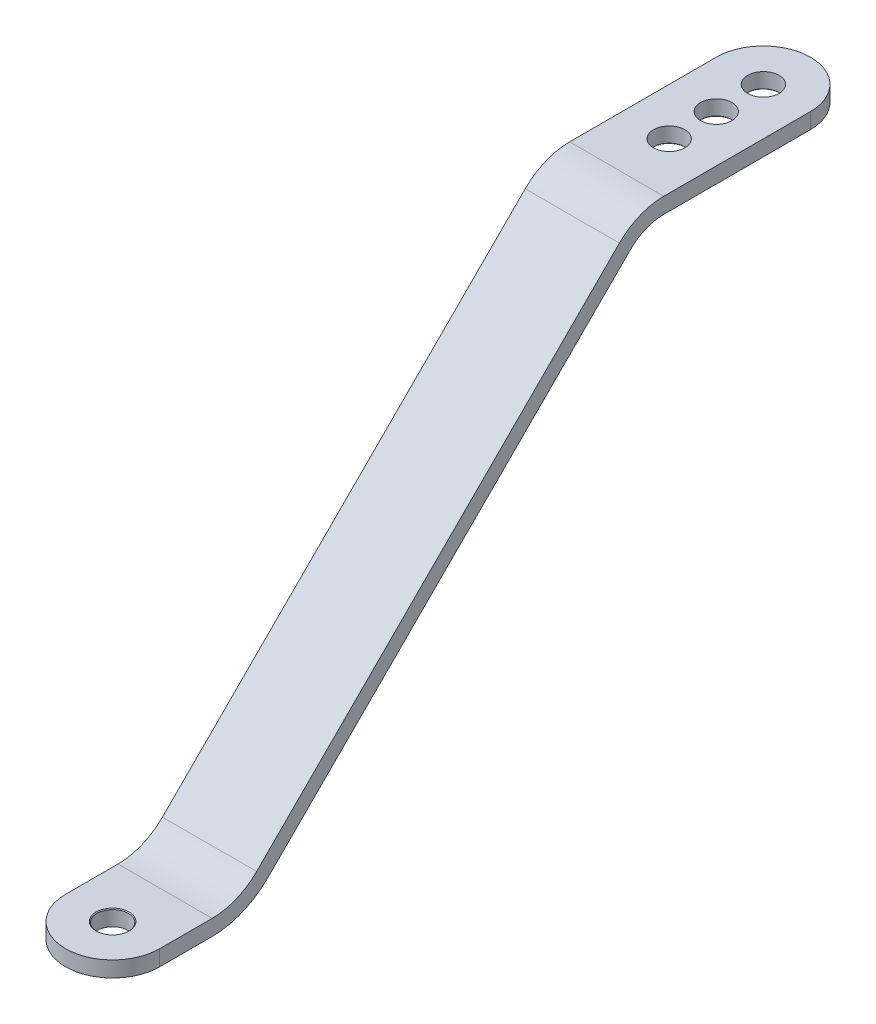
SolidWorks part; units mm, degrees
ref_plane "Front Plane" through (0, 0, 0) normal (0, 0, 1) x (1, 0, 0)
ref_plane "Top Plane" through (0, 0, 0) normal (0, 1, 0) x (1, 0, 0)
ref_plane "Right Plane" through (0, 0, 0) normal (1, 0, 0) x (0, 0, -1)
sketch "Sketch2" plane through (0, 0, 0) normal (1, 0, 0) x (0, 0, -1)
  line L0 (-263.2446, 0) -> (-182.6867, 0)
  line L1 (-146.7656, 14.879) -> (146.7656, 308.4102)
  line L2 (182.6867, 323.2892) -> (339.4446, 323.2892)
  line L3 (0, 0) -> (339.4446, 0) construction
  line L4 (-263.2446, -12.7) -> (-182.6867, -12.7)
  line L5 (-137.7854, 5.8987) -> (155.7459, 299.43)
  line L6 (182.6867, 310.5892) -> (339.4446, 310.5892)
  line L7 (-263.2446, 0) -> (-263.2446, -12.7)
  line L8 (339.4446, 323.2892) -> (339.4446, 310.5892)
  arc A0 (146.7656, 308.4102) -> (182.6867, 323.2892) centre (182.6867, 272.4892) cw
  arc A1 (-182.6867, 0) -> (-146.7656, 14.879) centre (-182.6867, 50.8) ccw
  arc A2 (-182.6867, -12.7) -> (-137.7854, 5.8987) centre (-182.6867, 50.8) ccw
  arc A3 (155.7459, 299.43) -> (182.6867, 310.5892) centre (182.6867, 272.4892) cw
  point P9 (0, 161.6446)
  point P14 (161.6446, 323.2892)
  point P17 (-161.6446, 0)
  dimension "D5" = 50.8
  dimension "D1" = 101.6
  dimension "D2" = 457.2
  dimension "D3" = 177.8
  dimension "D4" = 45
  dimension "D6" = 12.7
extrude "Boss-Extrude1" add sketch "Sketch2" along normal blind 76.2
fillet "Fillet1" 2 edges at (76.2, -6.35, 263.2446) (0, -6.35, 263.2446) type full round first side face at (76.2, 155.7657, -14.2584) second side face at (0, 155.7657, -14.2584) middle face at (38.1, -6.35, 263.2446)
fillet "Fillet2" 2 edges at (0, 316.9392, -339.4446) (76.2, 316.9392, -339.4446) type full round first side face at (0, 155.7657, -20.6084) second side face at (76.2, 155.7657, -20.6084) middle face at (38.1, 316.9392, -339.4446)
hole_wizard "1 (1) Diameter Hole1" positions "Sketch3" profile "Sketch4" hole size "1" standard "ANSI Inch" end condition through all
sketch "Sketch3" plane through (0, 0, 0) normal (0, 1, 0) x (1, 0, 0)
  point P0 (38.1, -225.1446)
sketch "Sketch4" plane through (38.1, 0, 225.1446) normal (1, 0, 0) x (0, 0, 1)
  line L0 (0, 0) -> (0, 12.7)
  line L1 (0, 12.7) -> (12.7, 12.7)
  line L2 (12.7, 12.7) -> (12.7, 0.635)
  line L3 (12.7, 0.635) -> (13.335, 0)
  line L5 (13.335, 0) -> (0, 0)
  line L6 (-12.7, 0.635) -> (-13.335, 0) construction
  line L11 (0, -6.35) -> (0, 107.95) construction
  dimension "Thru Hole Dia." = 25.4
  dimension "Thru Hole Depth" = 12.7
  dimension "Near C'Sink Dia." = 26.67
  dimension "Near C'Sink Angle" = 90
hole_wizard "1 (1) Diameter Hole2" positions "3DSketch1" profile "Sketch7" hole size "1" standard "ANSI Inch" end condition through all
sketch3d "3DSketch1"
  line L0 (38.1, 310.5892, -301.3446) -> (38.1, 323.2892, -301.3446) construction
  point P0 (38.1, 310.5892, -301.3446)
sketch "Sketch7" plane through (38.1, 310.5892, -301.3446) normal (1, 0, 0) x (0, 0, -1)
  line L0 (0, 0) -> (0, 12.7)
  line L1 (0, 12.7) -> (12.7, 12.7)
  line L2 (12.7, 12.7) -> (12.7, 0.635)
  line L3 (12.7, 0.635) -> (13.335, 0)
  line L5 (13.335, 0) -> (0, 0)
  line L6 (-12.7, 0.635) -> (-13.335, 0) construction
  line L11 (0, -6.35) -> (0, 107.95) construction
  dimension "Thru Hole Dia." = 25.4
  dimension "Thru Hole Depth" = 12.7
  dimension "Near C'Sink Dia." = 26.67
  dimension "Near C'Sink Angle" = 90
pattern_linear "LPattern1" count 3 spacing 38.1 along (0, 0, 1) of "1 (1) Diameter Hole2"
